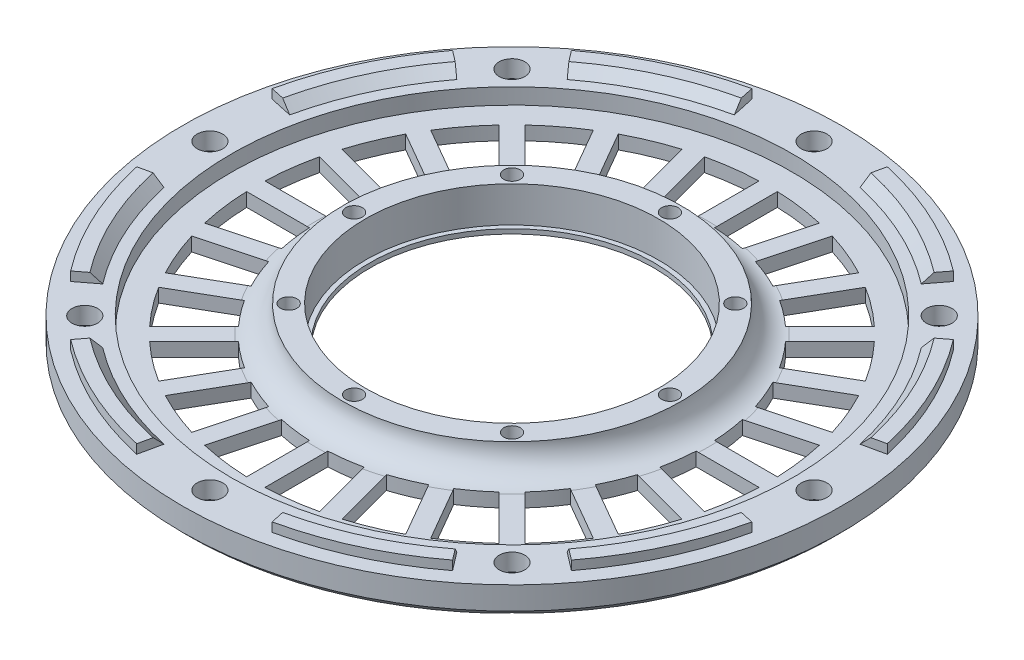
SolidWorks part; units mm, degrees
ref_plane "Front Plane" through (0, 0, 0) normal (0, 0, 1) x (1, 0, 0)
ref_plane "Top Plane" through (0, 0, 0) normal (0, 1, 0) x (1, 0, 0)
ref_plane "Right Plane" through (0, 0, 0) normal (1, 0, 0) x (0, 0, -1)
sketch "Sketch1" plane through (0, 0, 0) normal (0, 1, 0) x (1, 0, 0)
  circle A0 centre (0, 0) radius 16.025
  circle A1 centre (0, 0) radius 36
  dimension "D1" = 32.05
  dimension "D2" = 72
extrude "Boss-Extrude1" add sketch "Sketch1" along normal blind 1
sketch "Sketch2" plane through (0, 0, 0) normal (0, -1, 0) x (1, 0, 0)
  circle A0 centre (0, 0) radius 17.25 construction
  circle A1 centre (0, 0) radius 18.5 construction
  circle A2 centre (0, 0) radius 18.5
  circle A3 centre (0, 0) radius 16.025 construction
  circle A4 centre (0, 0) radius 16.025
  arc A5 (-1.2, 18.461) -> (-12.2054, 13.9025) centre (0, 0) ccw construction
  point P3 (0, -17.25)
extrude "Boss-Extrude2" add sketch "Sketch2" against normal offset from surface (3.9 mm away) 3.9 up to face at (0, 0, 36)
fillet "Fillet1" radius 2.9 1 edges at (0, 1, 18.5)
sketch "Sketch4" plane through (0, 0, 0) normal (0, 1, 0) x (1, 0, 0)
  circle A0 centre (0, 0) radius 15.525
  circle A1 centre (0, 0) radius 36
  circle A2 centre (0, 0) radius 36
  circle A3 centre (0, 0) radius 16.025 construction
  dimension "D2" = 0.5
  dimension "D1" = 0
extrude "Boss-Extrude3" add sketch "Sketch4" against normal blind 0.5
sketch "Sketch5" plane through (0, 1, 0) normal (0, 1, 0) x (1, 0, 0)
  line L0 (27.99, -0.75) -> (19.9859, -0.75) construction
  line L1 (19.9859, 0.75) -> (27.99, 0.75) construction
  line L2 (27.99, -0.75) -> (19.9859, -0.75) construction
  line L3 (19.9859, 0.75) -> (27.99, 0.75) construction
  line L4 (0, 0) -> (36, 0) construction
  line L5 (0, 0) -> (34.7733, 9.3175) construction
  line L6 (34.7733, 9.3175) -> (36, 0) construction
  line L7 (0, 0) -> (35.3867, 4.6587) construction
  line L8 (27.99, 1) -> (21.1263, 1)
  line L9 (27.295, 6.2784) -> (20.6653, 4.502)
  line L10 (27.99, -1) -> (21.1263, -1)
  line L11 (27.295, -6.2784) -> (20.6653, -4.502)
  line L12 (26.7774, -8.2103) -> (20.1477, -6.4338)
  line L13 (24.74, -13.129) -> (18.796, -9.6971)
  line L14 (23.74, -14.861) -> (17.796, -11.4292)
  line L15 (20.499, -19.0848) -> (15.6457, -14.2315)
  line L16 (19.0848, -20.499) -> (14.2315, -15.6457)
  line L17 (14.861, -23.74) -> (11.4292, -17.796)
  line L18 (13.129, -24.74) -> (9.6971, -18.796)
  line L19 (8.2103, -26.7774) -> (6.4338, -20.1477)
  line L20 (6.2784, -27.295) -> (4.502, -20.6653)
  line L21 (1, -27.99) -> (1, -21.1263)
  line L22 (-1, -27.99) -> (-1, -21.1263)
  line L23 (-6.2784, -27.295) -> (-4.502, -20.6653)
  line L24 (-8.2103, -26.7774) -> (-6.4338, -20.1477)
  line L25 (-13.129, -24.74) -> (-9.6971, -18.796)
  line L26 (-14.861, -23.74) -> (-11.4292, -17.796)
  line L27 (-19.0848, -20.499) -> (-14.2315, -15.6457)
  line L28 (-20.499, -19.0848) -> (-15.6457, -14.2315)
  line L29 (-23.74, -14.861) -> (-17.796, -11.4292)
  line L30 (-24.74, -13.129) -> (-18.796, -9.6971)
  line L31 (-26.7774, -8.2103) -> (-20.1477, -6.4338)
  line L32 (-27.295, -6.2784) -> (-20.6653, -4.502)
  line L33 (-27.99, -1) -> (-21.1263, -1)
  line L34 (-27.99, 1) -> (-21.1263, 1)
  line L35 (-27.295, 6.2784) -> (-20.6653, 4.502)
  line L36 (-26.7774, 8.2103) -> (-20.1477, 6.4338)
  line L37 (-24.74, 13.129) -> (-18.796, 9.6971)
  line L38 (-23.74, 14.861) -> (-17.796, 11.4292)
  line L39 (-20.499, 19.0848) -> (-15.6457, 14.2315)
  line L40 (-19.0848, 20.499) -> (-14.2315, 15.6457)
  line L41 (-14.861, 23.74) -> (-11.4292, 17.796)
  line L42 (-13.129, 24.74) -> (-9.6971, 18.796)
  line L43 (-8.2103, 26.7774) -> (-6.4338, 20.1477)
  line L44 (-6.2784, 27.295) -> (-4.502, 20.6653)
  line L45 (-1, 27.99) -> (-1, 21.1263)
  line L46 (1, 27.99) -> (1, 21.1263)
  line L47 (6.2784, 27.295) -> (4.502, 20.6653)
  line L48 (8.2103, 26.7774) -> (6.4338, 20.1477)
  line L49 (13.129, 24.74) -> (9.6971, 18.796)
  line L50 (14.861, 23.74) -> (11.4292, 17.796)
  line L51 (19.0848, 20.499) -> (14.2315, 15.6457)
  line L52 (20.499, 19.0848) -> (15.6457, 14.2315)
  line L53 (23.74, 14.861) -> (17.796, 11.4292)
  line L54 (24.74, 13.129) -> (18.796, 9.6971)
  line L55 (26.7774, 8.2103) -> (20.1477, 6.4338)
  line L56 (0, 0) -> (21.1263, 1) construction
  circle A0 centre (0, 0) radius 21.15 construction
  circle A2 centre (0, 0) radius 36 construction
  arc A3 (21.1263, 1) -> (20.6653, 4.502) centre (0, 0) ccw
  arc A4 (27.99, 1) -> (27.295, 6.2784) centre (0, 0) ccw
  arc A5 (27.295, -6.2784) -> (27.99, -1) centre (0, 0) ccw
  arc A6 (20.6653, -4.502) -> (21.1263, -1) centre (0, 0) ccw
  arc A7 (24.74, -13.129) -> (26.7774, -8.2103) centre (0, 0) ccw
  arc A8 (18.796, -9.6971) -> (20.1477, -6.4338) centre (0, 0) ccw
  arc A9 (20.499, -19.0848) -> (23.74, -14.861) centre (0, 0) ccw
  arc A10 (15.6457, -14.2315) -> (17.796, -11.4292) centre (0, 0) ccw
  arc A11 (14.861, -23.74) -> (19.0848, -20.499) centre (0, 0) ccw
  arc A12 (11.4292, -17.796) -> (14.2315, -15.6457) centre (0, 0) ccw
  arc A13 (8.2103, -26.7774) -> (13.129, -24.74) centre (0, 0) ccw
  arc A14 (6.4338, -20.1477) -> (9.6971, -18.796) centre (0, 0) ccw
  arc A15 (1, -27.99) -> (6.2784, -27.295) centre (0, 0) ccw
  arc A16 (1, -21.1263) -> (4.502, -20.6653) centre (0, 0) ccw
  arc A17 (-6.2784, -27.295) -> (-1, -27.99) centre (0, 0) ccw
  arc A18 (-4.502, -20.6653) -> (-1, -21.1263) centre (0, 0) ccw
  arc A19 (-13.129, -24.74) -> (-8.2103, -26.7774) centre (0, 0) ccw
  arc A20 (-9.6971, -18.796) -> (-6.4338, -20.1477) centre (0, 0) ccw
  arc A21 (-19.0848, -20.499) -> (-14.861, -23.74) centre (0, 0) ccw
  arc A22 (-14.2315, -15.6457) -> (-11.4292, -17.796) centre (0, 0) ccw
  arc A23 (-23.74, -14.861) -> (-20.499, -19.0848) centre (0, 0) ccw
  arc A24 (-17.796, -11.4292) -> (-15.6457, -14.2315) centre (0, 0) ccw
  arc A25 (-26.7774, -8.2103) -> (-24.74, -13.129) centre (0, 0) ccw
  arc A26 (-20.1477, -6.4338) -> (-18.796, -9.6971) centre (0, 0) ccw
  arc A27 (-27.99, -1) -> (-27.295, -6.2784) centre (0, 0) ccw
  arc A28 (-21.1263, -1) -> (-20.6653, -4.502) centre (0, 0) ccw
  arc A29 (-27.295, 6.2784) -> (-27.99, 1) centre (0, 0) ccw
  arc A30 (-20.6653, 4.502) -> (-21.1263, 1) centre (0, 0) ccw
  arc A31 (-24.74, 13.129) -> (-26.7774, 8.2103) centre (0, 0) ccw
  arc A32 (-18.796, 9.6971) -> (-20.1477, 6.4338) centre (0, 0) ccw
  arc A33 (-20.499, 19.0848) -> (-23.74, 14.861) centre (0, 0) ccw
  arc A34 (-15.6457, 14.2315) -> (-17.796, 11.4292) centre (0, 0) ccw
  arc A35 (-14.861, 23.74) -> (-19.0848, 20.499) centre (0, 0) ccw
  arc A36 (-11.4292, 17.796) -> (-14.2315, 15.6457) centre (0, 0) ccw
  arc A37 (-8.2103, 26.7774) -> (-13.129, 24.74) centre (0, 0) ccw
  arc A38 (-6.4338, 20.1477) -> (-9.6971, 18.796) centre (0, 0) ccw
  arc A39 (-1, 27.99) -> (-6.2784, 27.295) centre (0, 0) ccw
  arc A40 (-1, 21.1263) -> (-4.502, 20.6653) centre (0, 0) ccw
  arc A41 (6.2784, 27.295) -> (1, 27.99) centre (0, 0) ccw
  arc A42 (4.502, 20.6653) -> (1, 21.1263) centre (0, 0) ccw
  arc A43 (13.129, 24.74) -> (8.2103, 26.7774) centre (0, 0) ccw
  arc A44 (9.6971, 18.796) -> (6.4338, 20.1477) centre (0, 0) ccw
  arc A45 (19.0848, 20.499) -> (14.861, 23.74) centre (0, 0) ccw
  arc A46 (14.2315, 15.6457) -> (11.4292, 17.796) centre (0, 0) ccw
  arc A47 (23.74, 14.861) -> (20.499, 19.0848) centre (0, 0) ccw
  arc A48 (17.796, 11.4292) -> (15.6457, 14.2315) centre (0, 0) ccw
  arc A49 (26.7774, 8.2103) -> (24.74, 13.129) centre (0, 0) ccw
  arc A50 (20.1477, 6.4338) -> (18.796, 9.6971) centre (0, 0) ccw
  dimension "D1" = 15
  dimension "D2" = 1
  dimension "D4" = 21.15
  dimension "D3" = 24
extrude "Cut-Extrude1" cut sketch "Sketch5" against normal through all both and the other way through all
sketch "Sketch7" plane through (0, 3.9, 0) normal (0, 1, 0) x (1, 0, 0)
  line L0 (0, 0) -> (0, 17.25) construction
  circle A0 centre (0, 17.25) radius 0.9
  circle A1 centre (12.1976, 12.1976) radius 0.9
  circle A2 centre (17.25, 0) radius 0.9
  circle A3 centre (12.1976, -12.1976) radius 0.9
  circle A4 centre (0, -17.25) radius 0.9
  circle A5 centre (-12.1976, -12.1976) radius 0.9
  circle A6 centre (-17.25, 0) radius 0.9
  circle A7 centre (-12.1976, 12.1976) radius 0.9
  point P21 (0, 0)
  dimension "D1" = 1.8
  dimension "D2" = 8
extrude "Cut-Extrude2" cut sketch "Sketch7" against normal through all
sketch "Sketch8" plane through (0, 1, 0) normal (0, 1, 0) x (1, 0, 0)
  arc A0 (-30.6392, -0.8144) -> (-29.9521, -6.5032) centre (0, 0) ccw construction
  arc A1 (-30.6392, -0.8144) -> (-29.9521, -6.5032) centre (0, 0) ccw construction
  arc A2 (-29.9521, 6.5032) -> (-30.6392, 0.8144) centre (0, 0) ccw construction
  arc A3 (-29.9521, 6.5032) -> (-30.6392, 0.8144) centre (0, 0) ccw construction
  circle A5 centre (0, 0) radius 30.65
  circle A6 centre (0, 0) radius 36 construction
  circle A7 centre (0, 0) radius 36
extrude "Boss-Extrude4" add sketch "Sketch8" along normal blind 1.7378
sketch "Sketch9" plane through (0, 2.7378, 0) normal (0, 1, 0) x (1, 0, 0)
  line L0 (0, 0) -> (-29.9521, 6.5032) construction
  line L1 (0, 0) -> (-29.9521, -6.5032) construction
  line L2 (-29.9521, 6.5032) -> (-29.9521, -6.5032) construction
  line L3 (-27.3707, 21.0023) -> (-23.9196, 18.3542) construction
  line L4 (0, 0) -> (0, 36) construction
  line L5 (0, 0) -> (-25.4558, 25.4558) construction
  line L6 (-24.3163, 18.6585) -> (0, 0) construction
  line L7 (-24.3163, 18.6585) -> (-28.5607, 21.9154) construction
  line L8 (-29.9521, 6.5032) -> (-35.1803, 7.6384) construction
  line L9 (-27.3521, 20.862) -> (-25.3687, 19.3401)
  line L10 (-31.2086, 14.47) -> (0, 0) construction
  line L11 (-33.5954, 7.3966) -> (-31.1523, 6.8662)
  line L12 (-7.3966, 33.5954) -> (-6.8662, 31.1523)
  line L13 (-20.862, 27.3521) -> (-19.3401, 25.3687)
  arc A0 (-29.9521, 6.5032) -> (-24.3163, 18.6585) centre (0, 0) cw construction
  arc A1 (-35.1803, 7.6384) -> (-28.5607, 21.9154) centre (0, 0) cw construction
  circle A2 centre (0, 0) radius 36 construction
  circle A3 centre (0, 0) radius 30.65 construction
  arc A4 (-27.2914, 20.9414) -> (-33.6168, 7.2989) centre (0, 0) ccw construction
  arc A5 (-31.1523, 6.8662) -> (-25.3687, 19.3401) centre (0, 0) cw
  arc A6 (-33.5954, 7.3966) -> (-27.3521, 20.862) centre (0, 0) cw
  circle A7 centre (0, 0) radius 36 construction
  arc A8 (-6.8662, 31.1523) -> (-19.3401, 25.3687) centre (0, 0) ccw
  arc A9 (-7.3966, 33.5954) -> (-20.862, 27.3521) centre (0, 0) ccw
  dimension "D2" = 0.1
  dimension "D3" = 45
  dimension "D4" = 0.1
  dimension "D1" = 2.5
extrude "Boss-Extrude5" add sketch "Sketch9" along normal blind 1
ref_axis "Axis1" through (0, -0.72, 0) along (0, 1, 0)
pattern_circular "CirPattern1" count 4 over 360 about axis through (0, -0.72, 0) along (0, 1, 0) of "Boss-Extrude5"
chamfer "Chamfer1" distance 1 angle 45 8 edges at (-28.9406, 3.7378, -13.4184) (-13.4184, 3.7378, -28.9406) (13.4184, 3.7378, -28.9406) (28.9406, 3.7378, -13.4184) (28.9406, 3.7378, 13.4184) (13.4184, 3.7378, 28.9406) (-13.4184, 3.7378, 28.9406) (-28.9406, 3.7378, 13.4184)
sketch "Sketch10" plane through (0, 2.7378, 0) normal (0, 1, 0) x (1, 0, 0)
  line L0 (0, 0) -> (0, 36) construction
  circle A0 centre (0, 0) radius 36 construction
  circle A1 centre (0, 33) radius 1.4 construction
  circle A2 centre (0, 33) radius 1.4
  circle A3 centre (23.3345, 23.3345) radius 1.4
  circle A4 centre (33, 0) radius 1.4
  circle A5 centre (23.3345, -23.3345) radius 1.4
  circle A6 centre (0, -33) radius 1.4
  circle A7 centre (-23.3345, -23.3345) radius 1.4
  circle A8 centre (-33, 0) radius 1.4
  circle A9 centre (-23.3345, 23.3345) radius 1.4
  point P9 (0, 0)
  point P10 (0, 0)
  point P26 (0, 0)
  dimension "D1" = 8
extrude "Cut-Extrude3" cut sketch "Sketch10" against normal through all both and the other way through all
chamfer "Chamfer2" distance 0.75 angle 45 1 edges at (0, -0.5, 36)
hole_wizard "CSK for M2.5 Flat Head Machine Screw1" positions "Sketch11" profile "Sketch12" countersink size "M2.5" standard "ANSI Metric" end condition through all
sketch "Sketch11" plane through (0, -0.5, 0) normal (0, -1, 0) x (-1, 0, 0)
  point P0 (0, -33)
  point P3 (23.3345, -23.3345)
  point P6 (33, 0)
  point P9 (23.3345, 23.3345)
  point P12 (0, 33)
  point P15 (-23.3345, 23.3345)
  point P18 (-33, 0)
  point P21 (-23.3345, -23.3345)
sketch "Sketch12" plane through (0, -0.5, 33) normal (1, 0, 0) x (0, 0, -1)
  line L0 (0, 0) -> (0, 4.4)
  line L1 (0, 4.4) -> (1.35, 4.4)
  line L2 (1.35, 4.4) -> (1.35, 1.4)
  line L3 (1.35, 1.4) -> (2.75, 0)
  line L5 (2.75, 0) -> (0, 0)
  line L6 (-1.35, 1.4) -> (-2.75, 0) construction
  line L11 (0, -6.35) -> (0, 107.95) construction
  dimension "Thru Hole Dia." = 2.7
  dimension "Thru Hole Depth" = 4.4
  dimension "Near C'Sink Dia." = 5.5
  dimension "Near C'Sink Angle" = 90
